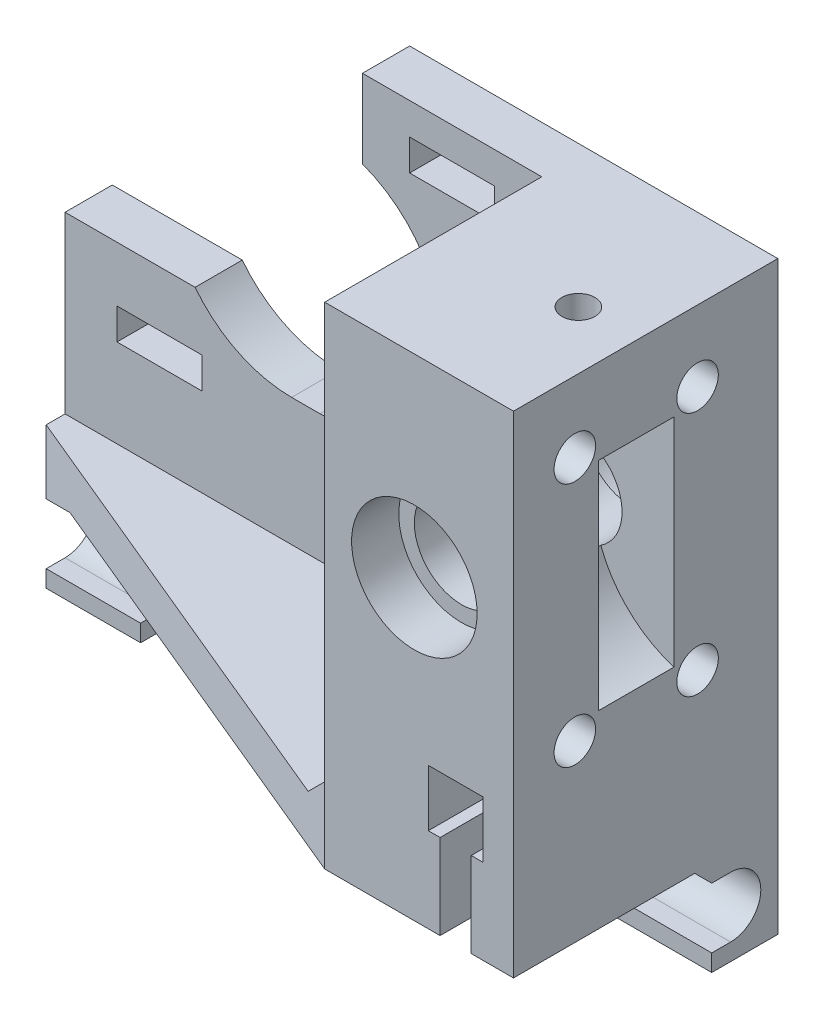
SolidWorks part; units mm, degrees
ref_plane "Front Plane" through (0, 0, 0) normal (0, 0, 1) x (1, 0, 0)
ref_plane "Top Plane" through (0, 0, 0) normal (0, 1, 0) x (1, 0, 0)
ref_plane "Right Plane" through (0, 0, 0) normal (1, 0, 0) x (0, 0, -1)
sketch "Sketch1" plane through (0, 0, 0) normal (0, 0, 1) x (1, 0, 0)
  line L0 (0, 0) -> (-60, 0) construction
  line L1 (-60, -31.5) -> (10.5, -31.5)
  line L2 (-60, -31.5) -> (-60, -8)
  line L3 (-28.5, 20.5) -> (10.5, 20.5)
  line L4 (10.5, -31.5) -> (10.5, 20.5)
  line L5 (-34.5, 0) -> (-34.5, -31.5) construction
  line L6 (-19, -15.5) -> (-19, 17.15) construction
  line L7 (-14.5, 15.5) -> (-50, 15.5) construction
  line L8 (-23.5, 13.85) -> (-14.5, 13.85)
  line L9 (-23.5, 13.85) -> (-23.5, 17.15)
  line L10 (-23.5, 17.15) -> (-14.5, 17.15)
  line L11 (-14.5, 13.85) -> (-14.5, 17.15)
  line L12 (-36, -12.9851) -> (-33, -12.9851)
  line L14 (-14.5, -13.85) -> (-14.5, -17.15)
  line L15 (-23.5, -17.15) -> (-14.5, -17.15)
  line L16 (-23.5, -13.85) -> (-23.5, -17.15)
  line L17 (-23.5, -13.85) -> (-14.5, -13.85)
  line L18 (-45.5, -13.85) -> (-54.5, -13.85)
  line L19 (-45.5, -13.85) -> (-45.5, -17.15)
  line L20 (-45.5, -17.15) -> (-54.5, -17.15)
  line L21 (-54.5, -13.85) -> (-54.5, -17.15)
  line L26 (-28.5, 20.5) -> (-28.5, 12.1804)
  line L27 (-60, -8) -> (-46.228, -8)
  line L28 (-50, -15.5) -> (-19, -15.5) [skipped]
  line L29 (-50, 15.5) -> (-50, -15.5) [skipped]
  circle A0 centre (0, 0) radius 5
  circle A1 centre (-34.5, 0) radius 15.5 construction
  arc A2 (-46.228, -8) -> (-36, -12.9851) centre (-36, 0) ccw
  arc A4 (-33, -12.9851) -> (-28.5, 12.1804) centre (-33, 0) ccw
  dimension "D1" = 10
  dimension "D6" = 34.5
  dimension "D8" = 3.3
  dimension "D2" = 31
  dimension "D7" = 6
  dimension "D3" = 52
  dimension "D4" = 60
  dimension "D5" = 31.5
  dimension "D9" = 9
  dimension "D10" = 3
  dimension "D11" = 1.5
  dimension "D12" = 8
  dimension "D13" = 10.5
extrude "Boss-Extrude1" add sketch "Sketch1" along normal blind 28
sketch "Sketch2" plane through (0, 0, 28) normal (0, 0, 1) x (1, 0, 0)
  line L0 (-60, -8) -> (-60, -31.5) construction
  line L1 (-60, -26.5) -> (-9.5, -26.5)
  line L2 (-60, -26.5) -> (-60, 20.5)
  line L3 (-60, 20.5) -> (-9.5, 20.5)
  line L4 (-9.5, -26.5) -> (-9.5, 20.5)
  line L5 (10.5, 20.5) -> (-28.5, 20.5) construction
  line L6 (0, 0) -> (-60, 0) construction
  circle A0 centre (-34.5, 0) radius 17.3693 construction
  dimension "D1" = 25
  dimension "D2" = 26.5
  dimension "D3" = 34.5
extrude "Cut-Extrude1" cut sketch "Sketch2" against normal offset from surface (23 mm away) 5 up to face at (-19, -15.5, 0)
sketch "Sketch3" plane through (0, 0, 28) normal (0, 0, 1) x (1, 0, 0)
  circle A0 centre (0, 0) radius 6.65
  dimension "D1" = 13.3
extrude "Cut-Extrude2" cut sketch "Sketch3" against normal blind 5
sketch "Sketch4" plane through (0, 0, 0) normal (0, 0, -1) x (-1, 0, 0)
  circle A0 centre (0, 0) radius 6.65
  dimension "D1" = 13.3
extrude "Cut-Extrude3" cut sketch "Sketch4" against normal blind 5
ref_plane "Plane1" through (0, 0, 11) normal (0, 0, 1) x (1, 0, 0)
sketch "Sketch5" plane through (0, 0, 11) normal (0, 0, 1) x (1, 0, 0)
  line L0 (0, 0) -> (14, 0) construction
  circle A0 centre (14, 0) radius 12
  dimension "D2" = 24
  dimension "D1" = 14
extrude "Cut-Extrude4" cut sketch "Sketch5" along normal blind 8
ref_plane "Plane2" through (0, -22.5, 0) normal (0, -1, 0) x (1, 0, 0)
sketch "Sketch6" plane through (0, -31.5, 0) normal (0, -1, 0) x (1, 0, 0)
  line L0 (0, 23) -> (0, 5) construction
  line L1 (5, 23) -> (-5, 23) construction
  line L2 (-6.65, 5) -> (6.65, 5) construction
  line L3 (10.5, 15) -> (2.75, 15) construction
  line L4 (10.5, 28) -> (10.5, 0) construction
  line L6 (2.75, 19) -> (2.75, 11) construction
  line L7 (2.725, 15) -> (2.725, 28)
  line L8 (-60, 28) -> (10.5, 28) construction
  line L9 (2.725, 28) -> (6.025, 28)
  line L10 (6.025, 28) -> (6.025, 15)
  arc A0 (2.725, 15) -> (6.025, 15) centre (4.375, 15) ccw
  point P21 (0, 15.1614)
  dimension "D1" = 1.65
  dimension "D2" = 4.375
extrude "Cut-Extrude5" cut sketch "Sketch6" against normal up to surface (9 mm away) up to plane "Plane2"
sketch "Sketch7" plane through (0, -22.5, 0) normal (0, -1, 0) x (1, 0, 0)
  line L0 (1.475, 28) -> (7.275, 28)
  line L2 (1.475, 28) -> (1.475, 13.3257)
  line L3 (1.475, 13.3257) -> (4.375, 11.6514)
  line L4 (4.375, 11.6514) -> (7.275, 13.3257)
  line L5 (7.275, 13.3257) -> (7.275, 28)
  line L7 (-60, 28) -> (2.725, 28) construction
  line L8 (6.025, 28) -> (10.5, 28) construction
  line L10 (3.7855, 18.0083) -> (1.1307, 16.4755) [skipped]
  line L11 (6.6855, 17.0147) -> (4.0307, 18.5474) [skipped]
  circle A0 centre (4.375, 15) radius 2.9 construction
  arc A1 (2.725, 15) -> (6.025, 15) centre (4.375, 15) ccw construction
  dimension "D1" = 5.8
extrude "Cut-Extrude6" cut sketch "Sketch7" against normal blind 6
sketch "Sketch8" plane through (0, -31.5, 0) normal (0, -1, 0) x (1, 0, 0)
  circle A0 centre (4.375, 15) radius 1.15
  arc A1 (2.725, 15) -> (6.025, 15) centre (4.375, 15) ccw construction
  dimension "D1" = 2.3
extrude "Cut-Extrude7" cut sketch "Sketch8" against normal through all
chamfer "Chamfer1" distance 21 distance2 50.5 1 edges at (-60, -29, 28) first distance on face at (-60, -22, 11)
sketch "Sketch9" plane through (10.5, 0, 0) normal (1, 0, 0) x (0, 0, -1)
  line L0 (-15, 11.4782) -> (-15, 17.5944) construction
  line L1 (-11, 11.4782) -> (-19, 11.4782) construction
  line L2 (0, 0) -> (-25.9492, 0) construction
  circle A0 centre (-8.5, 13) radius 2.2
  circle A1 centre (-21.5, 13) radius 2.2
  circle A2 centre (-8.5, -13) radius 2.2
  circle A3 centre (-21.5, -13) radius 2.2
  dimension "D1" = 4.4
  dimension "D2" = 6.5
  dimension "D3" = 13
extrude "Cut-Extrude8" cut sketch "Sketch9" against normal through all
sketch "Sketch10" plane through (-9.5, 0, 0) normal (-1, 0, 0) x (0, 0, 1)
  line L1 (4.85, 15.1073) -> (4.85, 10.8927)
  line L2 (4.85, 10.8927) -> (8.5, 8.7853)
  line L3 (8.5, 8.7853) -> (12.15, 10.8927)
  line L4 (12.15, 10.8927) -> (12.15, 15.1073)
  line L5 (12.15, 15.1073) -> (8.5, 17.2147)
  line L6 (8.5, 17.2147) -> (4.85, 15.1073)
  line L7 (25.15, 10.8927) -> (25.15, 15.1073)
  line L8 (25.15, 15.1073) -> (21.5, 17.2147)
  line L9 (21.5, 17.2147) -> (17.85, 15.1073)
  line L10 (17.85, 15.1073) -> (17.85, 10.8927)
  line L11 (17.85, 10.8927) -> (21.5, 8.7853)
  line L12 (21.5, 8.7853) -> (25.15, 10.8927)
  line L13 (25.15, -10.8927) -> (21.5, -8.7853)
  line L14 (21.5, -8.7853) -> (17.85, -10.8927)
  line L15 (17.85, -10.8927) -> (17.85, -15.1073)
  line L16 (17.85, -15.1073) -> (21.5, -17.2147)
  line L17 (21.5, -17.2147) -> (25.15, -15.1073)
  line L18 (25.15, -15.1073) -> (25.15, -10.8927)
  line L19 (12.15, -10.8927) -> (8.5, -8.7853)
  line L20 (8.5, -8.7853) -> (4.85, -10.8927)
  line L21 (4.85, -10.8927) -> (4.85, -15.1073)
  line L22 (4.85, -15.1073) -> (8.5, -17.2147)
  line L23 (8.5, -17.2147) -> (12.15, -15.1073)
  line L24 (12.15, -15.1073) -> (12.15, -10.8927)
  circle A0 centre (8.5, 13) radius 3.65 construction
  circle A1 centre (8.5, 13) radius 2.2 construction
  circle A2 centre (21.5, 13) radius 3.65 construction
  circle A3 centre (21.5, -13) radius 3.65 construction
  circle A4 centre (8.5, -13) radius 3.65 construction
  circle A5 centre (21.5, 13) radius 2.2 construction
  circle A6 centre (21.5, -13) radius 2.2 construction
  circle A7 centre (8.5, -13) radius 2.2 construction
  dimension "D1" = 7.3
extrude "Cut-Extrude9" cut sketch "Sketch10" against normal blind 7 and the other way blind 3
sketch "Sketch11" plane through (10.5, 0, 0) normal (1, 0, 0) x (0, 0, -1)
  line L0 (-28, -31.5) -> (0, -31.5) construction
  line L1 (0, -31.5) -> (-7, -31.5)
  line L2 (0, -31.5) -> (0, -41.5)
  line L3 (0, -41.5) -> (-7, -41.5)
  line L5 (-5, -36.5) -> (0, -36.5) construction
  line L6 (-5, -39.7) -> (-7, -39.7)
  line L7 (-7, -39.7) -> (-7, -41.5)
  line L8 (-5, -33.3) -> (-7, -33.3)
  line L9 (-7, -33.3) -> (-7, -31.5)
  arc A0 (-5, -39.7) -> (-5, -33.3) centre (-5, -36.5) ccw
  point P13 (-7.0994, -36.5)
  dimension "D1" = 3.2
  dimension "D2" = 10
  dimension "D3" = 2
  dimension "D4" = 5
extrude "Boss-Extrude2" add sketch "Sketch11" against normal blind 10
pattern_linear "LPattern1" count 2 spacing 60.5 along (-1, 0, 0) of "Boss-Extrude2"
sketch "Sketch12" plane through (0, 20.5, 0) normal (0, 1, 0) x (1, 0, 0)
  circle A0 centre (4.375, -15) radius 1.75
  circle A1 centre (4.375, -15) radius 1.15 construction
  dimension "D1" = 3.5
extrude "Cut-Extrude10" cut sketch "Sketch12" against normal blind 10
chamfer "Chamfer2" distance 3 angle 45 1 edges at (-9.5, -26.5, 16.5)
chamfer "Chamfer3" distance 1.8 angle 45 2 edges at (-55, -31.5, 7)
